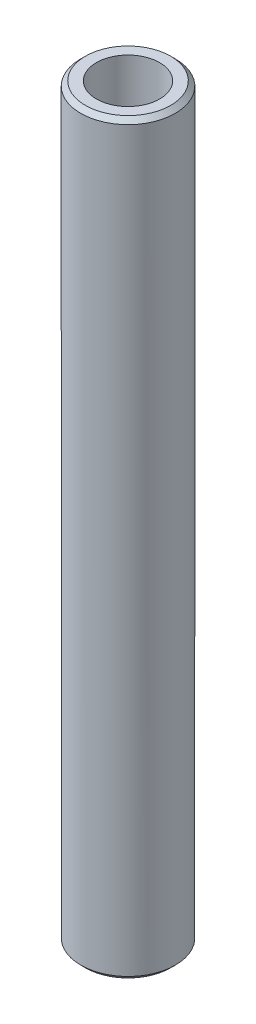
SolidWorks part; units mm, degrees
ref_plane "Front Plane" through (0, 0, 0) normal (0, 0, 1) x (1, 0, 0)
ref_plane "Top Plane" through (0, 0, 0) normal (0, 1, 0) x (1, 0, 0)
ref_plane "Right Plane" through (0, 0, 0) normal (1, 0, 0) x (0, 0, -1)
sketch "Sketch1" plane through (0, 0, 0) normal (0, 1, 0) x (1, 0, 0)
  circle A0 centre (0, 0) radius 35
  dimension "SHAFT_OD" = 70
extrude "Boss-Extrude1" add sketch "Sketch1" along normal blind 553.2372
sketch "Sketch2" plane through (0, 0, 0) normal (0, 1, 0) x (1, 0, 0)
  circle A0 centre (0, 0) radius 23.4024
  dimension "BORE_D" = 46.8049
extrude "Cut-Extrude1" cut sketch "Sketch2" along normal through all
chamfer "Chamfer1" distance 3.4045 angle 45 2 edges at (0, 553.2372, 35) (0, 0, 35)
